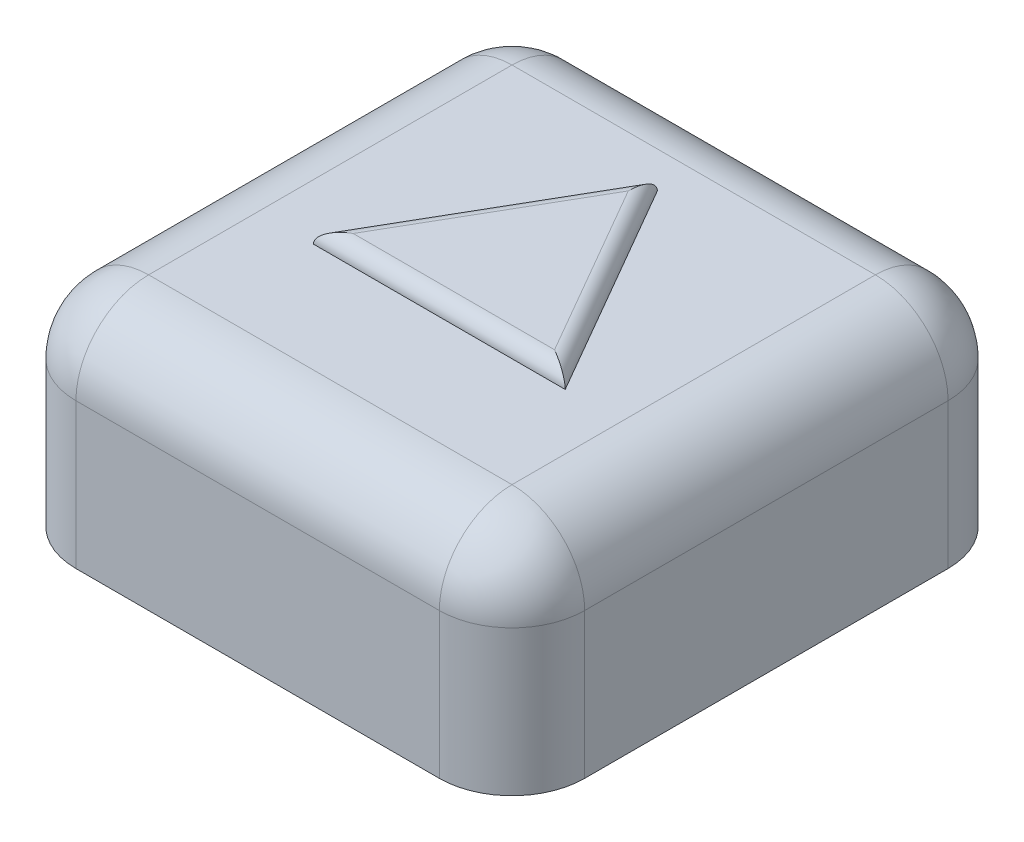
SolidWorks part; units mm, degrees
ref_plane "Front Plane" through (0, 0, 0) normal (0, 0, 1) x (1, 0, 0)
ref_plane "Top Plane" through (0, 0, 0) normal (0, 1, 0) x (1, 0, 0)
ref_plane "Right Plane" through (0, 0, 0) normal (1, 0, 0) x (0, 0, -1)
sketch "Sketch1" plane through (0, 0, 0) normal (0, 1, 0) x (1, 0, 0)
  line L1 (-3.5, 3.5) -> (3.5, 3.5)
  line L2 (-3.5, 3.5) -> (-3.5, -3.5)
  line L3 (-3.5, -3.5) -> (3.5, -3.5)
  line L4 (3.5, 3.5) -> (3.5, -3.5)
  line L5 (-3.5, 3.5) -> (3.5, -3.5) construction
  line L6 (-3.5, -3.5) -> (3.5, 3.5) construction
  point P0 (0, 0)
  dimension "D1" = 7
  dimension "D2" = 7
extrude "Boss-Extrude1" add sketch "Sketch1" along normal blind 3
fillet "Fillet1" radius 1 8 edges at (3.5, 1.5, -3.5) (-3.5, 1.5, -3.5) (-3.5, 1.5, 3.5) (3.5, 1.5, 3.5) (0, 3, -3.5) (-3.5, 3, 0) (0, 3, 3.5) (3.5, 3, 0)
sketch "Sketch2" plane through (0, 3, 0) normal (0, 1, 0) x (1, 0, 0)
  line L0 (0, 2) -> (-1.7321, -1)
  line L1 (-1.7321, -1) -> (1.7321, -1)
  line L2 (1.7321, -1) -> (0, 2)
  point P2 (0.866, 0.5)
  dimension "D1" = 60
  dimension "D2" = 60
  dimension "D3" = 60
  dimension "D4" = 1
  dimension "D5" = 1
  dimension "D6" = 1
extrude "Boss-Extrude2" add sketch "Sketch2" along normal blind 0.2
fillet "Fillet2" radius 0.2 3 edges at (-0.866, 3.2, -0.5) (0.866, 3.2, -0.5) (0, 3.2, 1)
